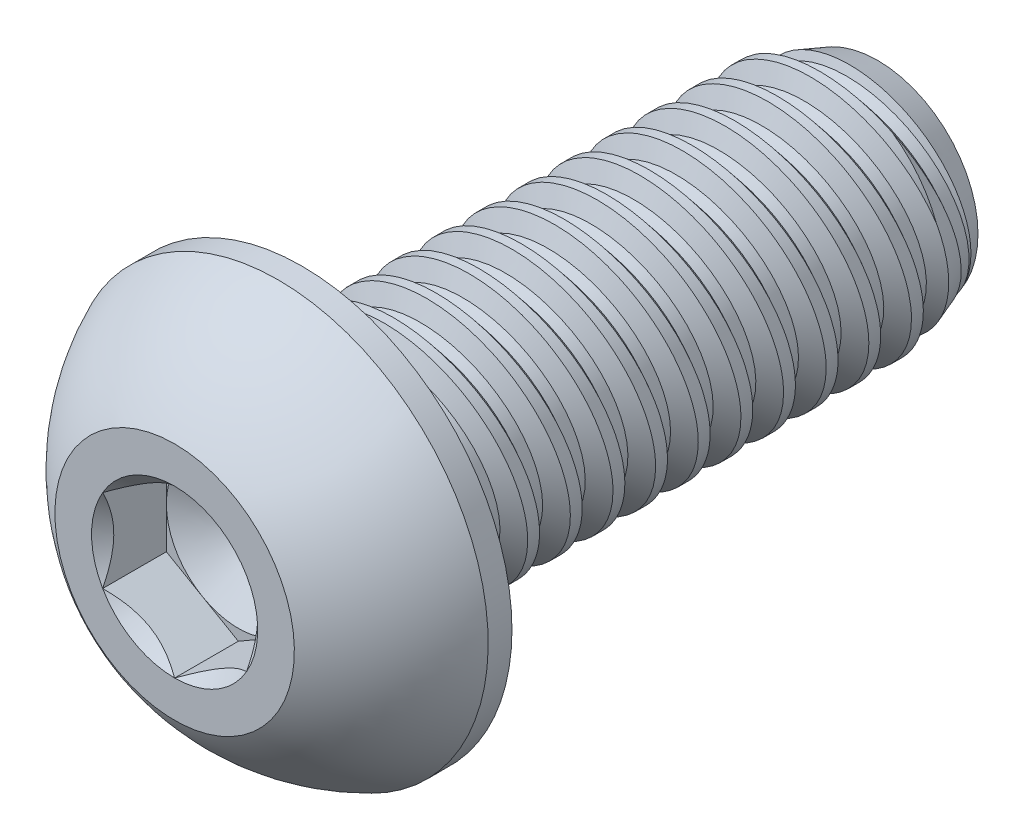
SolidWorks part; units mm, degrees
ref_plane "Front" through (0, 0, 0) normal (0, 0, 1) x (1, 0, 0)
ref_plane "Top" through (0, 0, 0) normal (0, 1, 0) x (1, 0, 0)
ref_plane "Right" through (0, 0, 0) normal (1, 0, 0) x (0, 0, -1)
sketch "Sketch1" plane through (0, 0, 0) normal (1, 0, 0) x (0, 0, -1)
  line L0 (0, 0) -> (-4.2164, 0) construction
  line L1 (0, 0) -> (19.05, 0)
  line L2 (0, 0) -> (0, 3.9624)
  line L3 (0, 3.9624) -> (19.05, 3.9624)
  line L4 (19.05, 0) -> (19.05, 3.9624)
  line L5 (0, -3.9624) -> (19.05, -3.9624) construction
  dimension "D1" = 19.05
  dimension "Thread Dia" = 7.9248
  dimension "Length" = 19.05
  dimension "Head Height" = 4.2164
revolve "Revolve1" add sketch "Sketch1" angle 360 about L0
ref_plane "Plane1" through (0, 0, 4.2164) normal (0, 0, 1) x (1, 0, 0)
sketch "Sketch2" plane through (0, 0, 0) normal (1, 0, 0) x (0, 0, -1)
  line L0 (0, 3.9624) -> (0, -3.9624) construction
  line L1 (0, -3.9624) -> (1.4111, -3.9624) construction
  line L2 (1.4111, -3.9624) -> (0, 3.9624) construction
  line L3 (0, 3.9624) -> (0.1737, 3.9933) construction
  line L4 (0.1737, 3.9933) -> (1.3893, 4.2098)
  line L5 (1.3893, 4.2098) -> (1.089, 3.3805)
  line L6 (1.089, 3.3805) -> (0.7417, 3.3187)
  line L7 (0.7417, 3.3187) -> (0.1737, 3.9933)
  line L8 (0.9154, 3.3496) -> (0.7815, 4.1015) construction
  line L9 (0, -3.9624) -> (19.05, -3.9624) construction
  line L10 (0, 3.9624) -> (19.05, 3.9624) construction
  line L12 (0.8062, 3.9624) -> (2.2173, -3.9624) construction
  line L13 (0, -0.2692) -> (3.0236, 0.2692) construction
  line L15 (0, 0) -> (0, 3.9624) construction
  point P19 (1.5118, 0)
  dimension "D1" = 60
  dimension "Thread Pitch" = 1.4111
  dimension "D2" = 0.1764
  dimension "D3" = 0.3528
  dimension "D4" = 1.4111
revolve "Cut-Revolve1" cut sketch "Sketch2" angle 360 about L13
sketch "Sketch3" plane through (0, 0, 0) normal (1, 0, 0) x (0, 0, -1)
  line L0 (19.05, 3.3187) -> (17.2814, 3.9624)
  line L1 (17.2814, 3.9624) -> (19.05, 3.9624)
  line L2 (19.05, 3.9624) -> (19.05, 3.3187)
  line L3 (0, 3.9624) -> (19.05, 3.9624) construction
  line L4 (19.05, 0) -> (19.05, 3.9624) construction
  line L5 (17.2814, 0) -> (0, 0) construction
  line L6 (17.2814, 3.9624) -> (17.2814, -3.9624) construction
  line L7 (0, -3.9624) -> (19.05, -3.9624) construction
  dimension "D1" = 20
  dimension "D2" = 7.9248
revolve "Cut-Revolve2" cut sketch "Sketch3" angle 360 about L5
pattern_linear "LPattern1" count 13 spacing 1.4111 along (0, 0, 1)
pattern_linear "LPattern2" count 2 spacing 1.4111 along (0, 0, 1)
sketch "Sketch4" plane through (0, 0, 0) normal (0, 0, 1) x (1, 0, 0)
  circle A0 centre (0, 0) radius 6.9469
  dimension "Head Dia" = 13.8938
extrude "Extrude1" add sketch "Sketch4" along normal up to surface (4.2164 mm away)
sketch "Sketch9" plane through (0, 0, 0) normal (1, 0, 0) x (0, 0, -1)
  line L0 (0, 6.9469) -> (-0.7874, 6.9469)
  line L1 (0, 6.9469) -> (0, 7.7343)
  line L2 (0, 7.7343) -> (-5.0038, 7.7343)
  line L3 (0, 0) -> (-4.2164, 0) construction
  line L4 (-5.0038, 7.7343) -> (-5.0038, 3.9624)
  line L5 (-5.0038, 3.9624) -> (-4.2164, 3.9624)
  line L6 (-4.2164, 6.9469) -> (-4.2164, -6.9469) construction
  line L10 (0, -6.9469) -> (0, 6.9469) construction
  line L11 (0, 6.9469) -> (-4.2164, 6.9469) construction
  line L12 (0, 3.9624) -> (19.05, 3.9624) construction
  arc A0 (-4.2164, 3.9624) -> (-0.7874, 6.9469) centre (2.2457, 0) cw
  dimension "Side Head Height" = 0.7874
revolve "Cut-Revolve3" cut sketch "Sketch9" angle 360 about L3
sketch "Sketch6" plane through (0, 0, 4.2164) normal (0, 0, 1) x (1, 0, 0)
  line L1 (0, -2.7496) -> (2.3812, -1.3748)
  line L2 (2.3812, -1.3748) -> (2.3812, 1.3748)
  line L3 (2.3812, 1.3748) -> (0, 2.7496)
  line L4 (0, 2.7496) -> (-2.3813, 1.3748)
  line L5 (-2.3813, 1.3748) -> (-2.3813, -1.3748)
  line L6 (-2.3813, -1.3748) -> (0, -2.7496)
  circle A0 centre (0, 0) radius 2.3813 construction
  dimension "Hex" = 4.7625
extrude "Cut-Extrude1" cut sketch "Sketch6" against normal blind 2.1082
sketch "Sketch7" plane through (0, 0, 4.2164) normal (0, 0, 1) x (1, 0, 0)
  circle A0 centre (0, 0) radius 2.7496
extrude "Cut-Extrude4" cut sketch "Sketch7" against normal blind 2.1082 draft 45
sketch "Sketch8" plane through (0, 0, 2.1082) normal (0, 0, 1) x (1, 0, 0)
  circle A0 centre (0, 0) radius 2.3813 construction
  circle A1 centre (0, 0) radius 2.3813
extrude "Cut-Extrude5" cut sketch "Sketch8" against normal blind 0.7027 draft 60
equation "\"D2@Sketch2\"=\"Thread Pitch@Sketch2\"/8"
equation "\"D3@Sketch2\"=\"Thread Pitch@Sketch2\"/4"
equation "\"D4@Sketch2\"=\"Thread Pitch@Sketch2\""
equation "\"D3@LPattern1\"=\"Thread Pitch@Sketch2\""
equation "\"D1@Cut-Extrude1\"=\"Head Height@Sketch1\"/2"
equation "\"D1@Cut-Extrude4\"=\"D1@Cut-Extrude1\""
equation "\"D1@Cut-Extrude5\"=\"D1@Cut-Extrude1\"/3"
equation "\"D1@LPattern1\"=\"D1@Sketch1\"/\"Thread Pitch@Sketch2\""
equation "\"D3@LPattern2\"=\"Thread Pitch@Sketch2\""
